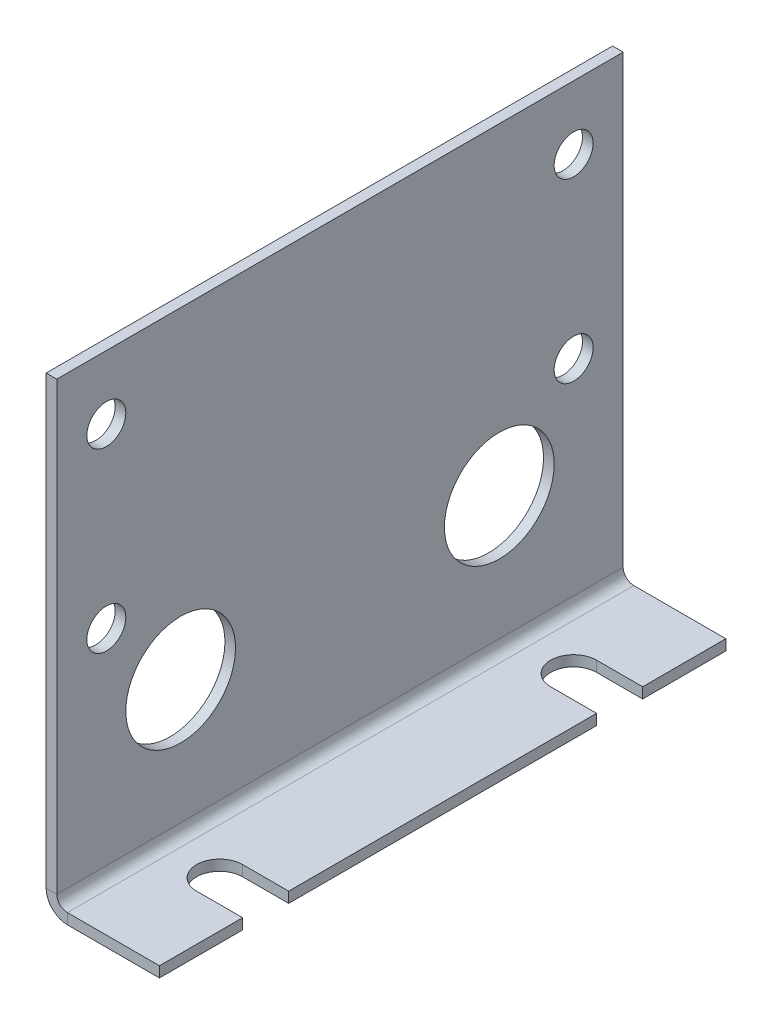
SolidWorks part; units mm, degrees
note: The reader was unsure of these and kept them because the rebuilt part matched: thickness of "Базовая кромка1", "Листовой металл3", "Листовой металл4", "Листовой металл5", "Листовой металл6"; bend radius of "Основание1".
material "Оцинкованная сталь"
ref_plane "Спереди" through (0, 0, 0) normal (0, 0, 1) x (1, 0, 0)
ref_plane "Сверху" through (0, 0, 0) normal (0, 1, 0) x (1, 0, 0)
ref_plane "Справа" through (0, 0, 0) normal (1, 0, 0) x (0, 0, -1)
sketch "Эскиз1" plane through (0, 0, 0) normal (0, 0, 1) x (1, 0, 0)
  line L0 (0, 129) -> (0, 0)
  line L1 (0, 0) -> (29, 0)
  dimension "D1" = 129
  dimension "D2" = 29
base flange "Базовая кромка1" sketch "Эскиз1" end condition mid plane depth 160 reverse direction no thickness 3 reverse thickness direction no bend radius 3
bend "Основание1" bend radius 3 bend angle 90 parameters "D5"=1
sketch "Эскиз6" plane through (0, 0, 0) normal (1, 0, 0) x (0, 0, -1)
  line L0 (-80, 129) -> (-80, 3) construction
  line L1 (-80, 129) -> (80, 129) construction
  circle A0 centre (-66, 111) radius 5.5
  circle A1 centre (66, 111) radius 5.5
  circle A2 centre (66, 61) radius 5.5
  circle A3 centre (-66, 61) radius 5.5
  dimension "D1" = 11
  dimension "D2" = 14
  dimension "D3" = 18
  dimension "D6" = 50
  dimension "D7" = 132
  dimension "D4" = 2
  dimension "D5" = 2
extrude "Вырез-Вытянуть1" cut sketch "Эскиз6" against normal blind 10 normal cut yes
sketch "Эскиз7" plane through (0, 0, 0) normal (1, 0, 0) x (0, 0, -1)
  line L0 (-80, 129) -> (80, 129) construction
  line L1 (-80, 129) -> (-80, 3) construction
  line L3 (0, 50) -> (0, -50) construction
  circle A0 centre (-45, 38) radius 15.5
  circle A1 centre (45, 38) radius 15.5
  dimension "D1" = 31
  dimension "D2" = 91
  dimension "D3" = 35
extrude "Вырез-Вытянуть2" cut sketch "Эскиз7" against normal blind 10 normal cut yes
sketch "Эскиз8" plane through (0, 0, 0) normal (0, 1, 0) x (1, 0, 0)
  line L0 (16, -50) -> (29, -50) construction
  line L1 (16, -43.5) -> (29, -43.5)
  line L2 (16, -56.5) -> (29, -56.5)
  line L3 (29, -80) -> (29, 80) construction
  line L4 (16, 50) -> (29, 50) construction
  line L5 (16, 56.5) -> (29, 56.5)
  line L6 (16, 43.5) -> (29, 43.5)
  line L7 (3, -80) -> (29, -80) construction
  arc A0 (16, -43.5) -> (16, -56.5) centre (16, -50) ccw
  arc A1 (29, -56.5) -> (29, -43.5) centre (29, -50) ccw
  arc A2 (16, 56.5) -> (16, 43.5) centre (16, 50) ccw
  arc A3 (29, 43.5) -> (29, 56.5) centre (29, 50) ccw
  point P2 (22.5, -50)
  point P12 (22.5, 50)
  dimension "D6" = 100
  dimension "D1" = 13
  dimension "D2" = 13
  dimension "D3" = 6.5
  dimension "D5" = 30
  dimension "D4" = 2
extrude "Вырез-Вытянуть3" cut sketch "Эскиз8" against normal blind 10 normal cut yes
sketch "Сгиб-Линии1" [suppressed] plane through (0, 0, 0) normal (0, 1, 0) x (1, 0, 0)
sketch "Граничная рамка1" [suppressed] plane through (0, 0, 0) normal (0, 1, 0) x (1, 0, 0)
sheet metal parameters "Листовой металл3" thickness 3 parameters "D1"=3
flat pattern "Развертка3" [suppressed]
sketch "Сгиб-Линии2" plane through (0, 0, 0) normal (0, 1, 0) x (1, 0, 0)
sketch "Граничная рамка2" [suppressed] plane through (0, 0, 0) normal (0, 1, 0) x (1, 0, 0)
bend of the flat pattern "Плоское состояние-<Основание1>1"
sheet metal parameters "Листовой металл4" thickness 3 parameters "D1"=3, "D7"=2
flat pattern "Развертка3" [suppressed]
sketch "Сгиб-Линии2" plane through (0, 0, 0) normal (0, 1, 0) x (1, 0, 0)
sketch "Граничная рамка2" [suppressed] plane through (0, 0, 0) normal (0, 1, 0) x (1, 0, 0)
bend of the flat pattern "Плоское состояние-<Основание1>1"
sheet metal parameters "Листовой металл5" thickness 3 parameters "D1"=3, "D7"=2
flat pattern "Развертка3" [suppressed]
sketch "Сгиб-Линии2" plane through (0, 0, 0) normal (0, 1, 0) x (1, 0, 0)
sketch "Граничная рамка2" [suppressed] plane through (0, 0, 0) normal (0, 1, 0) x (1, 0, 0)
bend of the flat pattern "Плоское состояние-<Основание1>1"
sheet metal parameters "Листовой металл6" thickness 3 parameters "D1"=3, "D7"=2
flat pattern "Развертка3"
sketch "Сгиб-Линии2" plane through (0, 0, 0) normal (1, 0, 0) x (0, 0, -1)
  line L0 (80, -0.5343) -> (-80, -0.5343) construction
  line L1 (80, -0.5343) -> (-80, -0.5343) construction
sketch3d "Граничная рамка2" [suppressed]
  line L0 (0, 0, 0) -> (160, 0, 0) construction
  line L1 (0, -159.0686, 0) -> (160, -159.0686, 0) construction
  line L2 (0, 0, 0) -> (0, -159.0686, 0) construction
  line L3 (160, 0, 0) -> (160, -159.0686, 0) construction
bend of the flat pattern "Плоское состояние-<Основание1>1"
